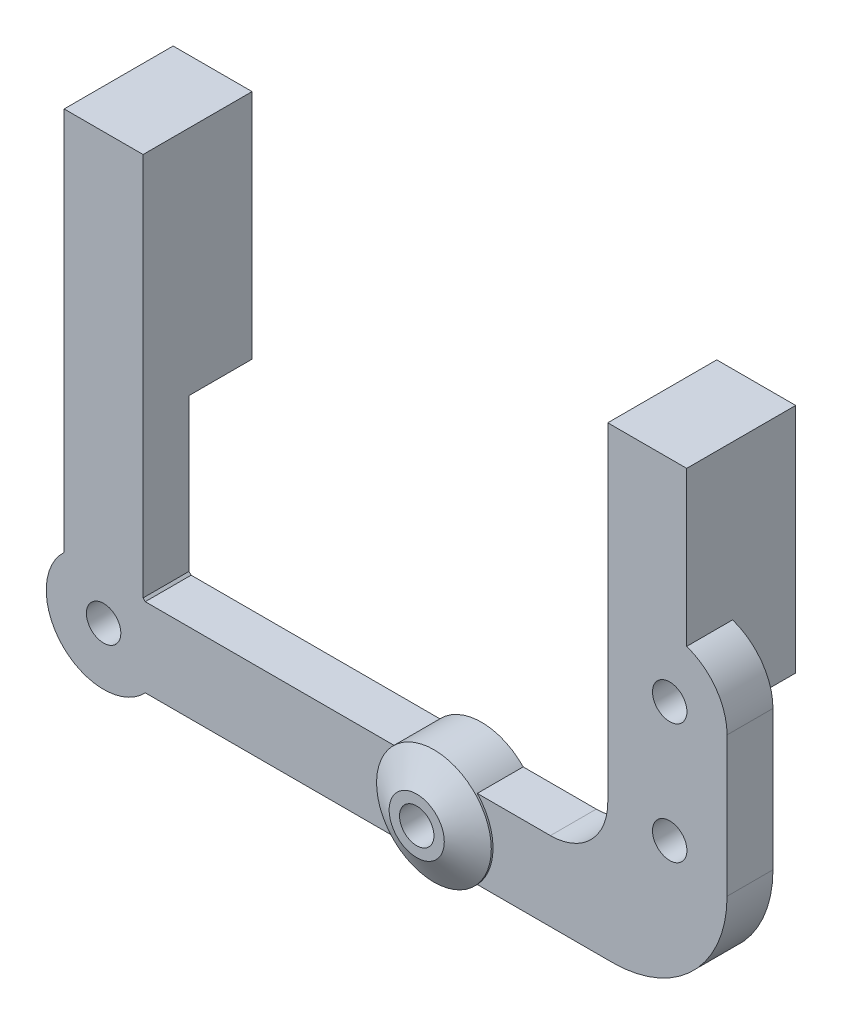
SolidWorks part; units mm, degrees
ref_plane "Alzado" through (0, 0, 0) normal (0, 0, 1) x (1, 0, 0)
ref_plane "Planta" through (0, 0, 0) normal (0, 1, 0) x (1, 0, 0)
ref_plane "Vista lateral" through (0, 0, 0) normal (1, 0, 0) x (0, 0, -1)
sketch "Croquis1" plane through (0, 0, 0) normal (0, 0, 1) x (1, 0, 0)
  line L0 (25.5, -3.4) -> (45.9, -3.4) construction
  line L1 (25.5, 10.1) -> (25.5, -16.9) construction
  line L2 (45.9, 1.84) -> (45.9, -8.64) construction
  line L3 (50.9, -10.34) -> (50.9, 1.84)
  line L4 (47.38, 20.2) -> (40.5, 20.2)
  line L8 (0, 20.2) -> (-6.88, 20.2)
  line L9 (-6.88, 20.2) -> (-6.88, -13.2714)
  line L17 (40.5, -8.46) -> (40.5, 20.2)
  line L18 (35.5, -13.46) -> (29.1286, -13.46)
  line L19 (0, 20.2) -> (0, -13.2714)
  line L20 (0.1886, -20.34) -> (21.8714, -20.34)
  line L23 (21.8714, -13.46) -> (0.1886, -13.46)
  line L24 (29.1286, -20.34) -> (40.9, -20.34)
  line L25 (47.38, 20.2) -> (47.38, 6.7611)
  circle A0 centre (45.9, 1.84) radius 1.5
  circle A1 centre (45.9, -8.64) radius 1.5
  circle A2 centre (25.5, -16.9) radius 1.5
  arc A3 (21.8714, -20.34) -> (29.1286, -20.34) centre (25.5, -16.9) ccw
  arc A4 (-6.88, -13.2714) -> (0.1886, -20.34) centre (-3.44, -16.9) ccw
  arc A7 (0.1886, -13.46) -> (0, -13.2714) centre (-3.44, -16.9) ccw
  arc A8 (29.1286, -13.46) -> (21.8714, -13.46) centre (25.5, -16.9) ccw
  circle A9 centre (-3.44, -16.9) radius 1.5
  arc A13 (40.5, -8.46) -> (35.5, -13.46) centre (35.5, -8.46) cw
  arc A14 (40.9, -20.34) -> (50.9, -10.34) centre (40.9, -10.34) ccw
  arc A15 (47.38, 6.7611) -> (50.9, 1.84) centre (45.7, 1.84) cw
  arc A16 (50.9, 1.84) -> (40.5, 1.84) centre (45.7, 1.84) ccw construction
  point P11 (0, 0)
  point P17 (50.9, 1.84)
  point P29 (47.38, 6.7611)
  dimension "D4" = 3
  dimension "D5" = 5
  dimension "D6" = 6.88
  dimension "D7" = 6.88
  dimension "D9" = 10
  dimension "D11" = 10
  dimension "D8" = 5
  dimension "D1" = 10.48
  dimension "D2" = 27
  dimension "D3" = 20.4
  dimension "D10" = 3.44
  dimension "D12" = 3.44
extrude "Saliente-Extruir1" add sketch "Croquis1" along normal blind 4
sketch "Croquis2" plane through (0, 0, 0) normal (0, 0, -1) x (-1, 0, 0)
  line L0 (-40.5, 20.2) -> (0, 20.2) construction
  line L1 (-40.5, 20.2) -> (-47.38, 20.2)
  line L2 (-40.5, 20.2) -> (-40.5, 0)
  line L3 (-40.5, 0) -> (-47.38, 0)
  line L4 (-47.38, 20.2) -> (-47.38, 0)
  line L5 (0, 0) -> (6.88, 0)
  line L6 (0, 0) -> (0, 20.2)
  line L7 (0, 20.2) -> (6.88, 20.2)
  line L8 (6.88, 0) -> (6.88, 20.2)
extrude "Saliente-Extruir2" add sketch "Croquis2" along normal up to surface (5.5 mm away)
sketch "Croquis3" plane through (0, 0, 4) normal (0, 0, 1) x (1, 0, 0)
  circle A0 centre (25.5, -16.9) radius 1.5
  circle A1 centre (25.5, -16.9) radius 5
  dimension "D1" = 3
  dimension "D2" = 10
extrude "Saliente-Extruir3" add sketch "Croquis3" along normal up to surface (1.65 mm away)
sketch "Croquis4" plane through (0, 0, 0) normal (0, 0, -1) x (-1, 0, 0)
  circle A0 centre (-25.5, -16.9) radius 1.5
  circle A1 centre (-45.9, 1.84) radius 1.5
  circle A2 centre (-45.9, -8.64) radius 1.5
  dimension "D1" = 3
extrude "Saliente-Extruir4" add sketch "Croquis4" against normal blind 1
sketch "Croquis5" plane through (0, 0, -5.5) normal (0, 0, -1) x (-1, 0, 0)
  circle A0 centre (-45.5, 5.4) radius 1.25
  circle A1 centre (-45.5, 14.8) radius 1.25
  circle A2 centre (5, 14.8) radius 1.25
  circle A3 centre (5, 5.4) radius 1.25
  dimension "D1" = 2.5
extrude "Cortar-Extruir1" cut sketch "Croquis5" against normal blind 8
chamfer "Chaflán1" distance 1.5 angle 60 1 edges at (30.5, -16.9, 5.65) first distance on face at (25.5, -16.9, 2)
